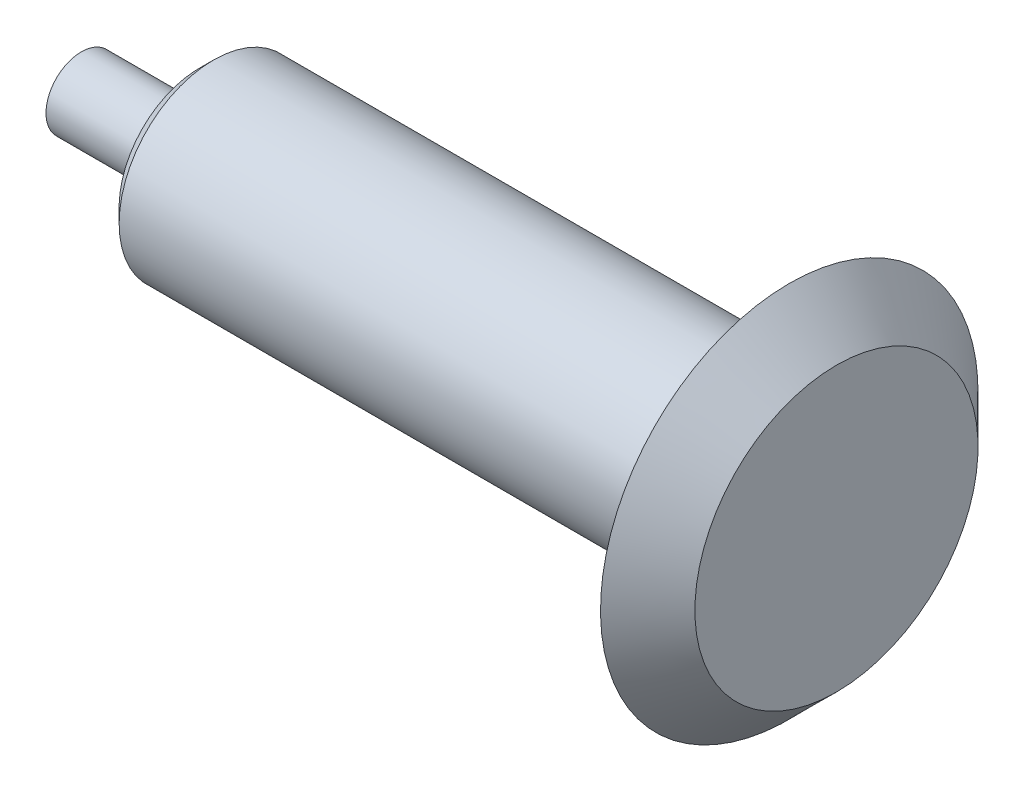
SolidWorks part; units mm, degrees
ref_plane "Front Plane" through (0, 0, 0) normal (0, 0, 1) x (1, 0, 0)
ref_plane "Top Plane" through (0, 0, 0) normal (0, 1, 0) x (1, 0, 0)
ref_plane "Right Plane" through (0, 0, 0) normal (1, 0, 0) x (0, 0, -1)
sketch "Sketch1" plane through (0, 0, 0) normal (0, 0, 1) x (1, 0, 0)
  line L0 (-80, 0) -> (-80, 7.5)
  line L1 (-80, 7.5) -> (-55, 7.5)
  line L2 (-55, 7.5) -> (-55, 20)
  line L3 (-55, 20) -> (62.9289, 20)
  line L6 (80, 40) -> (80, 0)
  line L7 (80, 0) -> (-80, 0)
  line L10 (70, 27.0711) -> (70, 40)
  line L11 (70, 40) -> (80, 40)
  line L12 (62.9289, 20) -> (70, 27.0711)
  point P2 (0, 0)
  point P6 (-80, 3.75)
  point P9 (80, 40)
  point P13 (70, 33.5355)
  dimension "D1" = 40
  dimension "D2" = 25
  dimension "D3" = 7.5
  dimension "D4" = 20
  dimension "D5" = 160
  dimension "D6" = 150
  dimension "D7" = 10
  dimension "D8" = 135
revolve "Revolve1" add sketch "Sketch1" angle 360 about L7
chamfer "Chamfer1" distance 10 angle 45 1 edges at (80, 40, 0)
chamfer "Chamfer2" distance 3 angle 45 1 edges at (-55, 20, 0)
